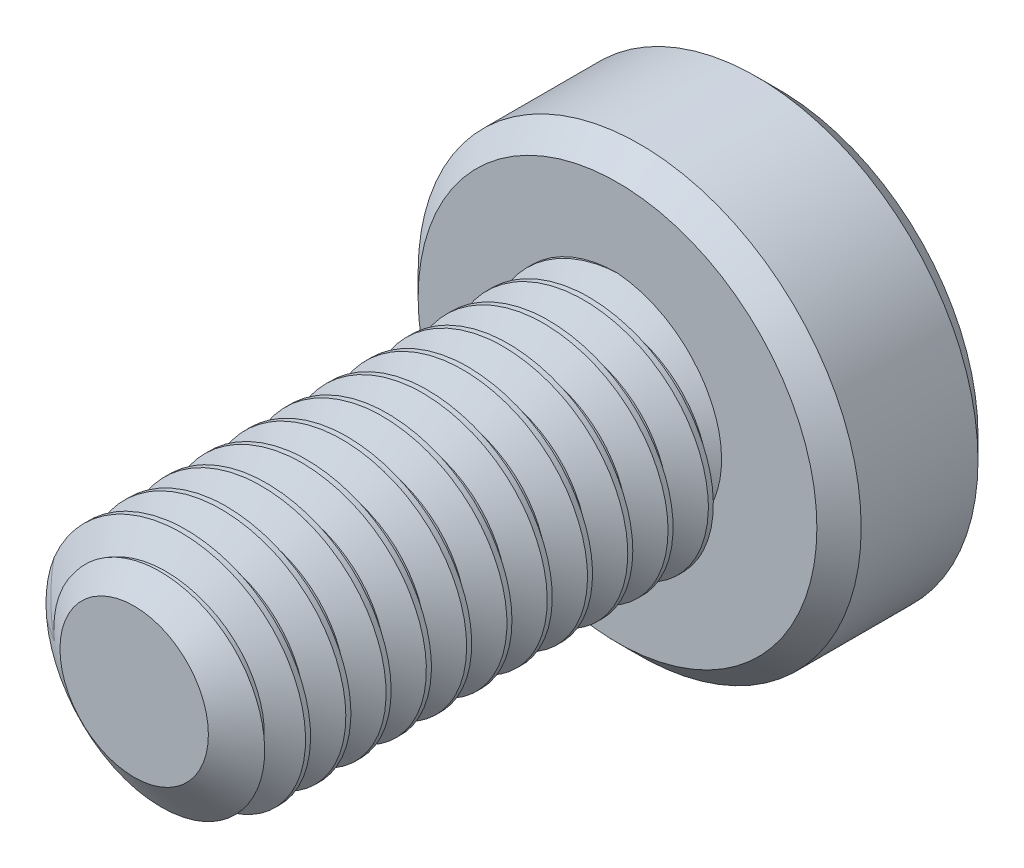
SolidWorks part; units mm, degrees
other "DetailItem1"
ref_plane "Front Plane" through (0, 0, 0) normal (0, 0, 1) x (1, 0, 0)
ref_plane "Top Plane" through (0, 0, 0) normal (0, 1, 0) x (1, 0, 0)
ref_plane "Right Plane" through (0, 0, 0) normal (1, 0, 0) x (0, 0, -1)
sketch "Sketch1" plane through (0, 0, 0) normal (0, 0, 1) x (1, 0, 0)
  circle A0 centre (0, 0) radius 1.5
  dimension "OD" = 3
extrude "Extrude1" add sketch "Sketch1" against normal blind 6
sketch "Sketch2" plane through (0, 0, 0) normal (0, 0, 1) x (1, 0, 0)
  circle A0 centre (0, 0) radius 1.5 construction
  circle A1 centre (0, 0) radius 1.5
curve "Helix/Spiral1" pitch 0.5 height 6.5 radius 1.5 centre (0, 0, 0) axis (0, 0, -1) start towards (0, 1, 0) parameters "pitch"=0.5
sketch "Sketch3" plane through (0, 0, 0) normal (1, 0, 0) x (0, 0, -1)
  line L0 (-0.4375, 1.5) -> (-0.25, 1.1752)
  line L1 (-0.25, 1.1752) -> (-0.1875, 1.1752)
  line L2 (-0.1875, 1.1752) -> (0, 1.5)
  line L3 (-0.4375, 1.5) -> (0, 1.5)
  line L4 (-0.2188, 1.5) -> (-0.2188, 1.1752) construction
  line L5 (-0.3438, 1.3376) -> (-0.0938, 1.3376) construction
  line L6 (0, 1.5) -> (0, -1.5) construction
  dimension "D1" = 0.0625
  dimension "D2" = 0.25
  dimension "D3" = 60
sweep "Cut-Sweep1" cut profiles "Sketch3" path "Helix/Spiral1" align with end faces yes
sketch "Sketch4" plane through (0, 0, 0) normal (1, 0, 0) x (0, 0, -1)
  line L0 (0.4053, 1.5) -> (0, 0.9212)
  line L1 (0, 0.9212) -> (0, 1.5)
  line L2 (0.4053, 1.5) -> (0, 1.5)
  line L3 (-0.4375, 1.5) -> (0, 1.5) construction
  line L4 (0, 0) -> (7.0209, 0) construction
  dimension "D1" = 55
  dimension "D2" = 0.254
revolve "Cut-Revolve1" cut sketch "Sketch4" angle 360 about L4
sketch "Sketch6" plane through (0, 0, -6) normal (0, 0, -1) x (-1, 0, 0)
  circle A0 centre (0, 0) radius 2.75
  dimension "head dia" = 5.5
extrude "Extrude2" add sketch "Sketch6" along normal blind 2
sketch "Sketch7" plane through (0, 0, -8) normal (0, 0, -1) x (-1, 0, 0)
  line L1 (0, 1.1547) -> (-1, 0.5774)
  line L2 (-1, 0.5774) -> (-1, -0.5774)
  line L3 (-1, -0.5774) -> (0, -1.1547)
  line L4 (0, -1.1547) -> (1, -0.5774)
  line L5 (1, -0.5774) -> (1, 0.5774)
  line L6 (1, 0.5774) -> (0, 1.1547)
  circle A0 centre (0, 0) radius 1 construction
  dimension "hex dia" = 2
extrude "Cut-Extrude1" cut sketch "Sketch7" against normal blind 1.5
sketch "Sketch8" plane through (0, 0, -8) normal (0, 0, -1) x (-1, 0, 0)
  circle A0 centre (0, 0) radius 1.1547
extrude "Cut-Extrude2" cut sketch "Sketch8" against normal through all draft 45
chamfer "Chamfer1" distance 0.275 angle 45 2 edges at (-2.75, 0, -8) (-2.75, 0, -6)
sketch "Sketch10" plane through (0, 0, -6) normal (0, 0, 1) x (1, 0, 0)
  circle A1 centre (0, 0) radius 1.5
  circle A2 centre (0, 0) radius 1.5
  dimension "D1" = 0
ref_plane "Plane1" through (0, 0, -30) normal (0, 0, 1) x (1, 0, 0)
extrude "partial thread" [suppressed] add sketch "Sketch10" along normal up to surface (20 mm away) separate body up to plane "Plane1"
chamfer "Chamfer2" [suppressed] distance 0.06 angle 45
combine bodies "Combine1" [suppressed] operation type add bodies to combine 107 108
sketch "Sketch9" plane through (0, 0, 0) normal (1, 0, 0) x (0, 0, -1)
  line L0 (0, 1.5) -> (0, -1.5) construction
  line L1 (1.25, 1.5) -> (1.25, -1.5) construction
  dimension "D1" = 1.25
equation "\"D3@Helix/Spiral1\" = \"screw length@Extrude1\"+\"pitch@Helix/Spiral1\""
equation "\"D1@Sketch3\" = \"pitch@Helix/Spiral1\"*.125"
equation "\"D2@Sketch3\" = \"pitch@Helix/Spiral1\"*.5"
equation "\"D1@Cut-Extrude1\" = \"hex dia@Sketch7\"*.75"
equation "\"D1@Chamfer1\" = \"head dia@Sketch6\"*.05"
equation "\"D1@Sketch9\" = \"pitch@Helix/Spiral1\"*2.5"
equation "\"D1@Chamfer2\"=\"OD@Sketch1\"*.02"
